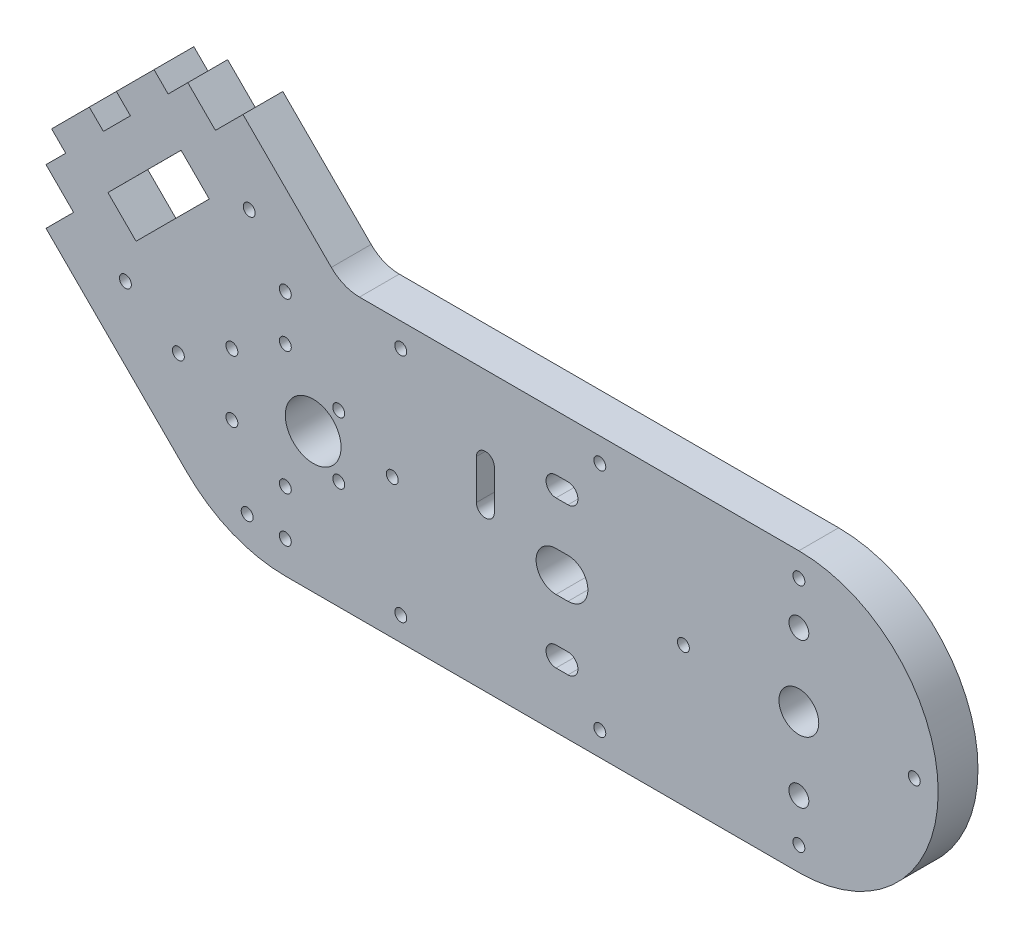
SolidWorks part; units mm, degrees
ref_plane "Front Plane" through (0, 0, 0) normal (0, 0, 1) x (1, 0, 0)
ref_plane "Top Plane" through (0, 0, 0) normal (0, 1, 0) x (1, 0, 0)
ref_plane "Right Plane" through (0, 0, 0) normal (1, 0, 0) x (0, 0, -1)
sketch "Sketch1" plane through (0, 0, 0) normal (0, 0, 1) x (1, 0, 0)
  line L0 (0, -35) -> (-129, -35)
  line L4 (0, 35) -> (-110.37, 35)
  line L9 (-58, 0) -> (-61, 0) construction
  line L10 (-58, -5) -> (-61, -5)
  line L11 (-58, 5) -> (-61, 5)
  line L13 (-58, 18.5) -> (-61, 18.5) construction
  line L14 (-58, 16) -> (-61, 16)
  line L15 (-58, 21) -> (-61, 21)
  line L17 (-58, -18.5) -> (-61, -18.5) construction
  line L18 (-58, -21) -> (-61, -21)
  line L19 (-58, -16) -> (-61, -16)
  line L20 (-78.75, 5) -> (-78.75, 15) construction
  line L21 (-81, 5) -> (-81, 15)
  line L22 (-76.5, 5) -> (-76.5, 15)
  line L25 (0, 0) -> (-129, 0) construction
  line L27 (-189.1079, 10.5847) -> (-182.1808, 17.5169)
  line L28 (-182.1808, 17.5169) -> (-146.5556, 53.168) construction
  line L29 (-146.5556, 53.168) -> (-139.6285, 60.1002)
  line L30 (-146.5556, 53.168) -> (-153.4878, 60.0952)
  line L31 (-182.1808, 17.5169) -> (-189.113, 24.444)
  line L32 (-189.113, 24.444) -> (-184.1651, 29.3955)
  line L33 (-184.1651, 29.3955) -> (-187.7019, 32.9298)
  line L34 (-153.4878, 60.0952) -> (-158.4357, 55.1436)
  line L35 (-158.4357, 55.1436) -> (-161.9726, 58.6778)
  line L36 (-187.7019, 32.9298) -> (-178.2301, 42.4085)
  line L37 (-184.1651, 29.3955) -> (-158.4357, 55.1436) construction
  line L38 (-178.2301, 42.4085) -> (-174.6933, 38.8742)
  line L39 (-161.9726, 58.6778) -> (-171.4443, 49.1992)
  line L40 (-171.4443, 49.1992) -> (-167.9075, 45.6649)
  line L41 (-174.6933, 38.8742) -> (-167.9075, 45.6649)
  line L43 (-189.1079, 10.5847) -> (-153.7397, -24.7578)
  line L44 (-171.3004, 42.2696) -> (-129, 0) construction
  line L45 (-139.6285, 60.1002) -> (-117.4393, 37.9271)
  line L46 (-173.5573, 26.1467) -> (-155.1792, 44.5382)
  line L47 (-155.1792, 44.5382) -> (-148.1081, 37.4671)
  line L48 (-148.1081, 37.4671) -> (-166.4929, 19.0823)
  line L49 (-166.4929, 19.0823) -> (-173.5573, 26.1467)
  line L54 (-129, 0) -> (-138.5766, -26.3114) construction
  line L55 (-129, 26.8701) -> (-129, -26.8701) construction
  line L56 (-155.8701, 0) -> (-102.1299, 0) construction
  line L57 (-129, 0) -> (-129, 15.5) construction
  line L58 (-129, 0) -> (-149.42, 0) construction
  line L59 (-122, 0) -> (-142.42, 0) construction
  line L60 (-142.42, 0) -> (-142.42, -7.7559) construction
  line L61 (-142.42, 7.7559) -> (-142.42, 0) construction
  line L62 (-122, 0) -> (-122, -7.7559) construction
  line L63 (-122, -7.7559) -> (-115.58, -7.7559) construction
  line L64 (-122, 0) -> (-122, 7.7559) construction
  line L65 (-122, 7.7559) -> (-115.58, 7.7559) construction
  line L66 (0, 0) -> (0, 18.25) construction
  circle A0 centre (0, 0) radius 5
  circle A1 centre (29, 0) radius 1.5
  circle A2 centre (0, -18.25) radius 2.5
  circle A3 centre (0, 18.25) radius 2.5
  arc A4 (0, -35) -> (0, 35) centre (0, 0) ccw
  circle A5 centre (0, 29) radius 1.5
  circle A6 centre (0, -29) radius 1.5
  circle A7 centre (-50, -29) radius 1.5
  circle A8 centre (-50, 29) radius 1.5
  circle A9 centre (-100, -29) radius 1.5
  circle A10 centre (-100, 29) radius 1.5
  arc A11 (-58, -5) -> (-58, 5) centre (-58, 0) ccw
  arc A12 (-61, 5) -> (-61, -5) centre (-61, 0) ccw
  arc A13 (-58, 16) -> (-58, 21) centre (-58, 18.5) ccw
  arc A14 (-61, 21) -> (-61, 16) centre (-61, 18.5) ccw
  arc A15 (-58, -21) -> (-58, -16) centre (-58, -18.5) ccw
  arc A16 (-61, -16) -> (-61, -21) centre (-61, -18.5) ccw
  circle A17 centre (-29, 0) radius 1.5
  arc A18 (-81, 5) -> (-76.5, 5) centre (-78.75, 5) ccw
  arc A19 (-76.5, 15) -> (-81, 15) centre (-78.75, 15) ccw
  arc A22 (-129, -35) -> (-153.7397, -24.7578) centre (-129, 0) cw
  arc A23 (-117.4393, 37.9271) -> (-110.37, 35) centre (-110.37, 45) ccw
  circle A27 centre (-169.167, 9.0363) radius 1.5
  circle A28 centre (-138.0656, 40.1604) radius 1.5
  circle A29 centre (-122, 0) radius 7
  circle A30 centre (-129, 26.8701) radius 1.5
  circle A31 centre (-155.8701, 0) radius 1.5
  circle A32 centre (-129, -26.8701) radius 1.5
  circle A33 centre (-102.1299, 0) radius 1.5
  circle A34 centre (-138.5766, -26.3114) radius 1.5
  circle A35 centre (-129, 15.5) radius 1.5
  circle A37 centre (-129, -15.5) radius 1.5
  circle A38 centre (-142.42, 7.7559) radius 1.5
  circle A39 centre (-142.42, -7.7559) radius 1.5
  circle A40 centre (-115.58, -7.7559) radius 1.5
  circle A41 centre (-115.58, 7.7559) radius 1.5
  point P13 (0, -29)
  point P29 (-59.5, 0)
  point P37 (-59.5, 18.5)
  point P45 (-59.5, -18.5)
  point P54 (-78.75, 10)
  point P74 (-102.28, 58.871)
  point P79 (-122, 0)
  point P86 (-164.3682, 35.3424)
  point P91 (-155.9618, 57.6194)
  point P102 (0, 0)
  point P117 (0, 0)
  dimension "D1" = 10
  dimension "D2" = 5
  dimension "D3" = 5
  dimension "D4" = 70
  dimension "D5" = 3
  dimension "D6" = 3
  dimension "D7" = 3
  dimension "D8" = 3
  dimension "D9" = 3
  dimension "D10" = 3
  dimension "D11" = 3
  dimension "D14" = 50
  dimension "D12" = 35
  dimension "D13" = 35
  dimension "D19" = 5
  dimension "D22" = 36.4
  dimension "D35" = 10
  dimension "D33" = 3
  dimension "D37" = 3
  dimension "D36" = 13
  dimension "D39" = 38
  dimension "D41" = 3
  dimension "D42" = 3
  dimension "D43" = 3
  dimension "D44" = 3
  dimension "D46" = 3
  dimension "D47" = 3
  dimension "D48" = 3
  dimension "D49" = 3
  dimension "D50" = 3
  dimension "D51" = 3
  dimension "D52" = 3
  dimension "D55" = 26.7761
  dimension "D15" = 129
  dimension "D16" = 58
  dimension "D17" = 11
  dimension "D18" = 4.5
  dimension "D20" = 10
  dimension "D21" = 110.37
  dimension "D23" = 50.4
  dimension "D24" = 13.4
  dimension "D25" = 9.8
  dimension "D26" = 9.8
  dimension "D27" = 7
  dimension "D28" = 9.8
  dimension "D29" = 9.8
  dimension "D30" = 5
  dimension "D31" = 5
  dimension "D32" = 13.4
  dimension "D34" = 31.3689
  dimension "D38" = 7
  dimension "D40" = 38
  dimension "D45" = 28
  dimension "D53" = 18.25
  dimension "D54" = 18.25
  dimension "D56" = 7.6513
extrude "Boss-Extrude1" add sketch "Sketch1" along normal blind 10
